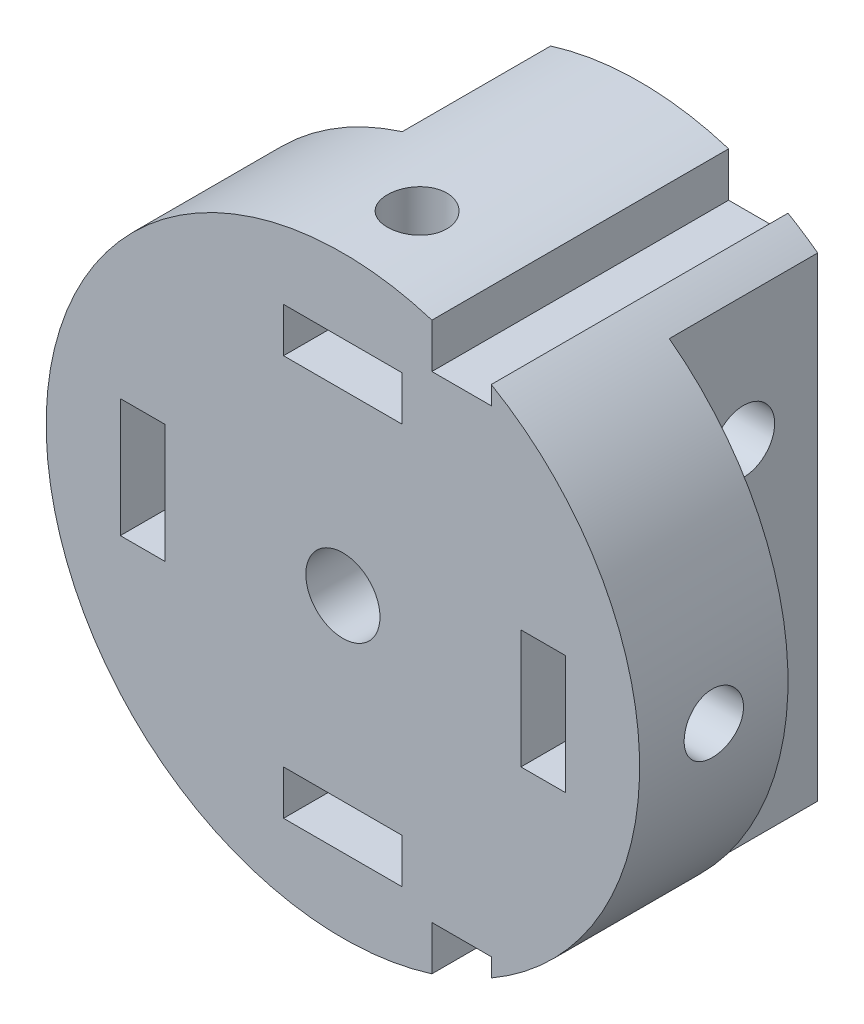
SolidWorks part; units mm, degrees
ref_plane "Front Plane" through (0, 0, 0) normal (1, 0, 0) x (0, 1, 0)
ref_plane "Top Plane" through (0, 0, 0) normal (0, 0, 1) x (0, 1, 0)
ref_plane "Right Plane" through (0, 0, 0) normal (0, 1, 0) x (-1, 0, 0)
sketch "Sketch3" plane through (0, 0, 0) normal (0, 0, 1) x (0, 1, 0)
  line L0 (0, 0) -> (25.4, 0) construction
  circle A0 centre (0, 0) radius 25.4
  circle A1 centre (0, 0) radius 3.175
  dimension "D1" = 50.8
  dimension "D2" = 6.35
extrude "base" add sketch "Sketch3" along normal blind 12.7
ref_plane "Plane1" through (-25.4, 0, 0) normal (-1, 0, 0) x (0, 0, 1)
sketch "Sketch6" plane through (0, 0, 0) normal (0, 0, -1) x (1, 0, 0)
  line L0 (0, 0) -> (15.24, 0) construction
  line L1 (15.24, 20.32) -> (-7.62, 20.32) construction
  line L2 (15.24, 20.32) -> (15.24, -20.32)
  line L3 (15.24, -20.32) -> (-7.62, -20.32) construction
  line L5 (-7.62, 24.2301) -> (-7.62, -24.2301)
  circle A0 centre (0, 0) radius 25.4 construction
  arc A1 (-7.62, 24.2301) -> (15.24, 20.32) centre (0, 0) cw
  arc A2 (-7.62, -24.2301) -> (15.24, -20.32) centre (0, 0) ccw
  circle A3 centre (0, 0) radius 3.175
  circle A4 centre (0, 0) radius 3.175 construction
  dimension "D1" = 22.86
  dimension "D2" = 15.24
extrude "upper_bolts_connection" add sketch "Sketch6" along normal blind 12.7
sketch "Sketch8" plane through (0, 0, -12.7) normal (0, 0, -1) x (1, 0, 0)
  line L1 (6.5991, 0) -> (3.2996, 5.715)
  line L2 (3.2996, 5.715) -> (-3.2996, 5.715)
  line L3 (-3.2996, 5.715) -> (-6.5991, 0)
  line L4 (-6.5991, 0) -> (-3.2996, -5.715)
  line L5 (-3.2996, -5.715) -> (3.2996, -5.715)
  line L6 (3.2996, -5.715) -> (6.5991, 0)
  circle A0 centre (0, 0) radius 5.715 construction
  dimension "D1" = 11.43
extrude "nut_hole" cut sketch "Sketch8" against normal blind 8.89
sketch "Sketch9" plane through (-7.62, 0, 0) normal (-1, 0, 0) x (0, 0, 1)
  circle A0 centre (-6.35, -9.525) radius 2.667
  circle A1 centre (-6.35, 9.525) radius 2.667
  circle A2 centre (-6.35, 9.525) radius 2.667 construction
  circle A3 centre (-6.35, -9.525) radius 2.667 construction
extrude "upper_boltholes" cut sketch "Sketch9" against normal up to next
sketch "Sketch13" plane through (-25.4, 0, 0) normal (-1, 0, 0) x (0, 0, 1)
  line L0 (0, 0) -> (12.7, 0) construction
  line L1 (12.2159, 0) -> (9.2829, 5.08) construction
  line L2 (9.2829, 5.08) -> (3.4171, 5.08) construction
  line L3 (3.4171, 5.08) -> (0.4841, 0)
  line L4 (0.4841, 0) -> (3.4171, -5.08)
  line L5 (3.4171, -5.08) -> (9.2829, -5.08) construction
  line L6 (9.2829, -5.08) -> (12.2159, 0) construction
  line L7 (12.7, -25.4) -> (12.7, 25.4) construction
  line L8 (3.4171, 5.08) -> (12.7, 5.08)
  line L9 (12.7, 5.08) -> (12.7, -5.08)
  line L10 (12.7, -5.08) -> (3.4171, -5.08)
  circle A0 centre (6.35, 0) radius 5.08 construction
  dimension "D1" = 10.16
extrude "nut_recess" cut sketch "Sketch13" against normal blind 3.81 from offset 6.35 offset against normal yes
sketch "Sketch14" plane through (-25.4, 0, 0) normal (-1, 0, 0) x (0, 0, 1)
  line L0 (0, 0) -> (12.7, 0) construction
  line L1 (12.7, -25.4) -> (12.7, 25.4) construction
  circle A0 centre (6.35, 0) radius 2.54
  dimension "D1" = 5.08
extrude "radial_bolt_hole" cut sketch "Sketch14" against normal blind 15.24
pattern_circular "CirPattern2" count 4 over 360 about axis through (0, 0, 12.7) along (0, 0, -1) of "radial_bolt_hole", "nut_recess" reverse direction yes
sketch "Sketch15" plane through (0, 0, -12.7) normal (0, 0, -1) x (1, 0, 0)
  line L0 (15.24, -20.32) -> (15.24, 20.32) construction
  line L1 (7.62, 24.2301) -> (12.7, 24.2301)
  line L2 (7.62, 24.2301) -> (7.62, 20.4201)
  line L3 (7.62, 20.4201) -> (12.7, 20.4201)
  line L5 (12.7, 20.4201) -> (12.7, 24.2301)
  arc A0 (15.24, 20.32) -> (-7.62, 24.2301) centre (0, 0) ccw construction
  dimension "D1" = 2.54
  dimension "D2" = 5.08
  dimension "D3" = 3.81
extrude "wire_passthrough" cut sketch "Sketch15" against normal up to next
mirror "wire_passthrough_mirror" about plane through (0, 0, 0) normal (0, 1, 0) of "wire_passthrough"
